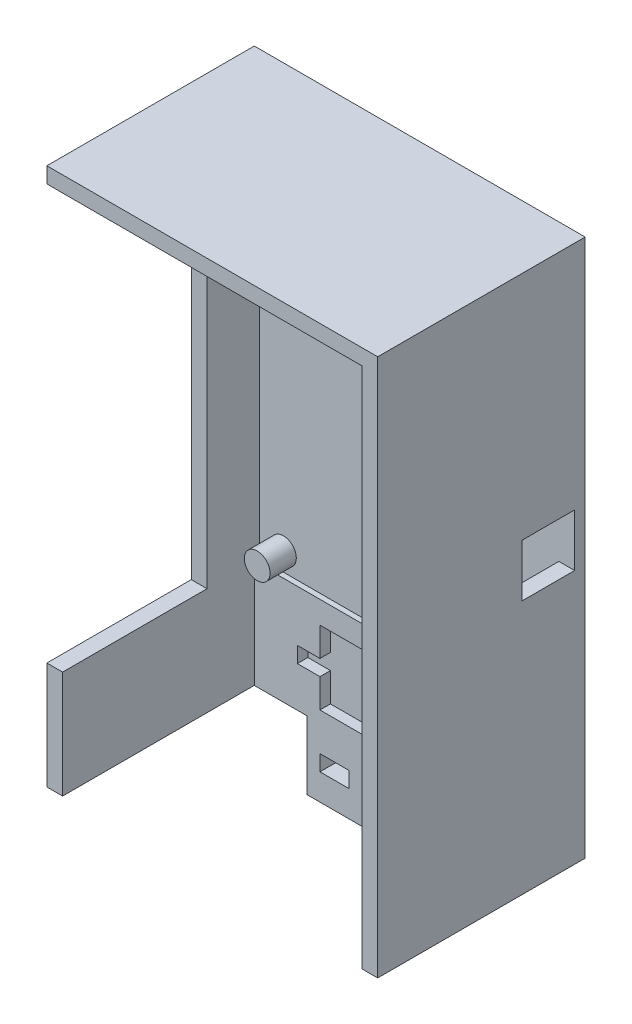
SolidWorks part; units mm, degrees
ref_plane "Přední rovina" through (0, 0, 0) normal (0, 0, 1) x (1, 0, 0)
ref_plane "Horní rovina" through (0, 0, 0) normal (0, 1, 0) x (1, 0, 0)
ref_plane "Pravá rovina" through (0, 0, 0) normal (1, 0, 0) x (0, 0, -1)
sketch "Skica1" plane through (0, 0, 0) normal (0, 0, 1) x (1, 0, 0)
  line L0 (13, -102.45) -> (13, -115.45)
  line L1 (0, 0) -> (63, 0)
  line L2 (0, 0) -> (0, -102.45)
  line L3 (0, -102.45) -> (13, -102.45)
  line L4 (63, 0) -> (63, -102.45)
  line L5 (13, -115.45) -> (50, -115.45)
  line L6 (50, -115.45) -> (50, -102.45)
  line L7 (50, -102.45) -> (63, -102.45)
  dimension "D1" = 102.45
  dimension "D2" = 63
  dimension "D3" = 13
  dimension "D4" = 13
  dimension "D5" = 13
extrude "Přidat vysunutím1" add sketch "Skica1" along normal blind 2
sketch "Skica3" plane through (0, 0, 2) normal (0, 0, 1) x (1, 0, 0)
  line L0 (63, -102.45) -> (63, 0) construction
  line L1 (63, 0) -> (0, 0) construction
  circle A0 centre (7.55, -6.45) radius 2.45
  circle A1 centre (7.55, -78.45) radius 2.45
  circle A2 centre (55.55, -78.45) radius 2.45
  circle A3 centre (55.55, -6.45) radius 2.45
  dimension "D1" = 4.9
  dimension "D2" = 48
  dimension "D4" = 7.45
  dimension "D5" = 6.45
  dimension "D3" = 72
extrude "Přidat vysunutím3" add sketch "Skica3" along normal blind 5
sketch "Skica4" plane through (0, 0, 2) normal (0, 0, 1) x (1, 0, 0)
  line L4 (63, 0) -> (63, -102.45)
  line L5 (3, -3) -> (60, -3)
  line L8 (60, -3) -> (60, -102.45)
  line L10 (60, -102.45) -> (63, -102.45)
  line L12 (0, 0) -> (0, -102.45)
  line L13 (0, 0) -> (63, 0)
  line L17 (3, -3) -> (3, -102.45)
  line L18 (0, -102.45) -> (13, -102.45) construction
  line L19 (3, -102.45) -> (0, -102.45)
  dimension "D1" = 3
  dimension "D2" = 3
  dimension "D3" = 3
extrude "Přidat vysunutím4" add sketch "Skica4" along normal blind 37.5
sketch "Skica8" plane through (60, 0, 0) normal (-1, 0, 0) x (0, 0, 1)
  line L0 (39.5, -3) -> (2, -3) construction
  line L1 (2, -54) -> (12, -54)
  line L2 (2, -54) -> (2, -44)
  line L3 (2, -44) -> (12, -44)
  line L4 (12, -54) -> (12, -44)
  line L5 (2, -3) -> (2, -102.45) construction
  point P6 (0, 0)
  point P7 (2, -30)
  dimension "D1" = 10
  dimension "D2" = 10
  dimension "D3" = 41
extrude "Odebrat vysunutím2" cut sketch "Skica8" against normal through all
sketch "Skica10" plane through (0, 0, 0) normal (-1, 0, 0) x (0, 0, 1)
  line L1 (12, -82) -> (39.5, -82)
  line L2 (12, -82) -> (12, -3)
  line L3 (12, -3) -> (39.5, -3)
  line L4 (39.5, -82) -> (39.5, -3)
  line L5 (39.5, 0) -> (39.5, -102.45) construction
  line L6 (0, 0) -> (0, -102.45) construction
  line L7 (39.5, 0) -> (0, 0) construction
  point P4 (0, 0)
  point P5 (4.3299, -75.4426)
  point P8 (0, 0)
  point P9 (0, -5.3087)
  point P12 (0, 0)
  point P13 (39.5, -6.5381)
  dimension "D1" = 3
  dimension "D2" = 12
  dimension "D3" = 79
extrude "Odebrat vysunutím3" cut sketch "Skica10" against normal up to surface (3 mm away) up to face at (3, -52.725, 20.75)
sketch "Skica11" plane through (0, 0, 2) normal (0, 0, 1) x (1, 0, 0)
  line L0 (3, -82) -> (60, -82)
  line L1 (3, -102.45) -> (3, -3) construction
  line L2 (60, -54) -> (60, -102.45) construction
  line L3 (60, -82) -> (60, -102.45)
  line L4 (60, -102.45) -> (50, -102.45)
  line L5 (50, -102.45) -> (50, -115.45)
  line L6 (50, -115.45) -> (13, -115.45)
  line L7 (13, -115.45) -> (13, -102.45)
  line L8 (13, -102.45) -> (13, -115.45) construction
  line L9 (3, -102.45) -> (13, -102.45) construction
  line L10 (13, -102.45) -> (3, -102.45)
  line L11 (3, -102.45) -> (3, -82)
  line L12 (3, -3) -> (60, -3) construction
  dimension "D1" = 79
extrude "Přidat vysunutím5" add sketch "Skica11" along normal blind 1
sketch "Skica12" plane through (0, 0, 3) normal (0, 0, 1) x (1, 0, 0)
  line L0 (3, -82) -> (3, -102.45) construction
  line L1 (15.5, -107.45) -> (21, -107.45)
  line L2 (15.5, -107.45) -> (15.5, -110.45)
  line L3 (15.5, -110.45) -> (21, -110.45)
  line L4 (21, -107.45) -> (21, -110.45)
  line L5 (15.5, -107.45) -> (21, -110.45) construction
  line L6 (15.5, -110.45) -> (21, -107.45) construction
  line L7 (13, -115.45) -> (50, -115.45) construction
  line L10 (15.5, -86.25) -> (15.5, -91.75)
  line L13 (15.5, -94.75) -> (15.5, -100.25)
  line L15 (11.2, -91.75) -> (15.5, -91.75)
  line L16 (11.2, -91.75) -> (11.2, -94.75)
  line L17 (11.2, -94.75) -> (15.5, -94.75)
  line L19 (15.5, -86.25) -> (46.5, -86.25)
  line L20 (46.5, -86.25) -> (46.5, -100.25)
  line L21 (46.5, -100.25) -> (15.5, -100.25)
  line L24 (60, -82) -> (3, -82) construction
  point P0 (18.25, -108.95)
  point P18 (0, 0)
  point P19 (15, -94.6635)
  dimension "D1" = 3
  dimension "D2" = 5.5
  dimension "D4" = 5
  dimension "D5" = 3
  dimension "D6" = 14
  dimension "D7" = 31
  dimension "D8" = 4.3
  dimension "D9" = 7.2
  dimension "D10" = 12.5
  dimension "D11" = 5.5
  dimension "D12" = 4.25
extrude "Odebrat vysunutím4" cut sketch "Skica12" against normal blind 2 contours L21 L13 L17 L16 L15 L10 L19 L20
extrude "Odebrat vysunutím5" cut sketch "Skica12<3>" against normal through all contours L4 L3 L2 L1
sketch "Skica12<3>" plane through (0, 0, 3) normal (0, 0, 1) x (1, 0, 0) same geometry as "Skica12"
